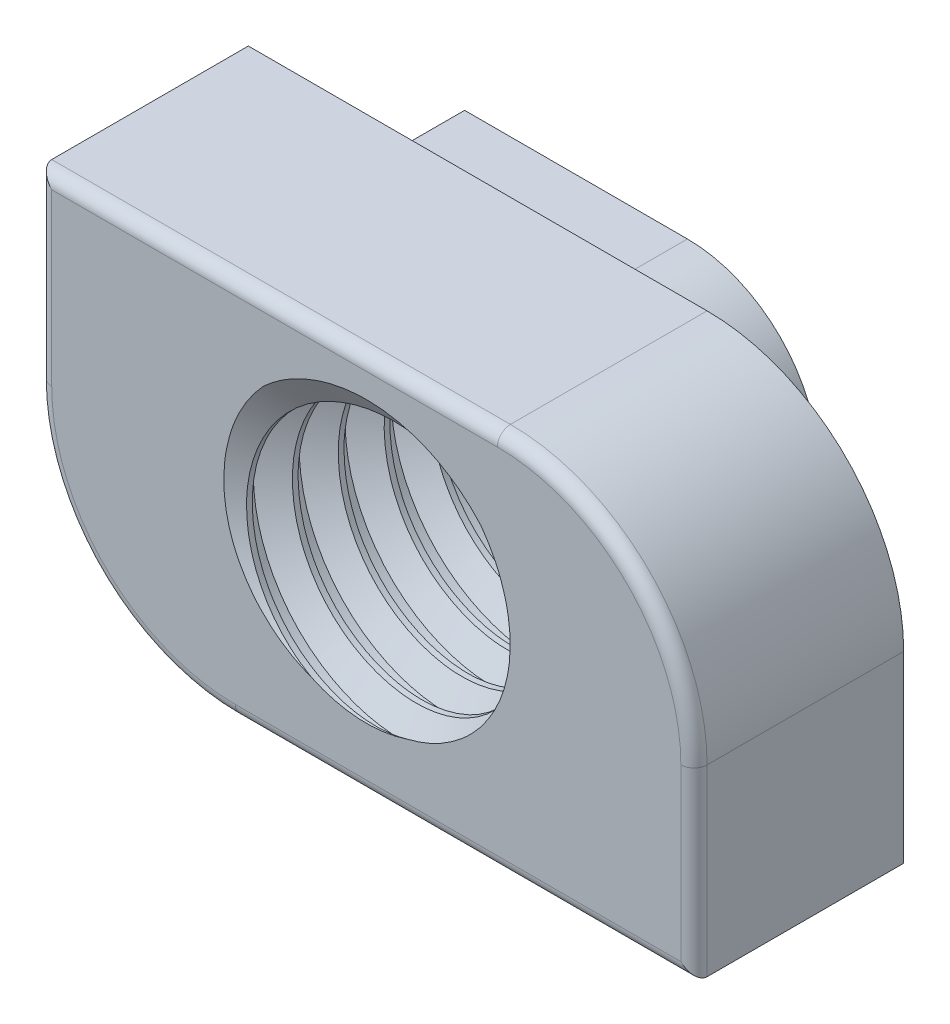
SolidWorks part; units mm, degrees
material "Hierro dúctil (SN)"
ref_plane "Alzado" through (0, 0, 0) normal (0, 0, 1) x (1, 0, 0)
ref_plane "Planta" through (0, 0, 0) normal (0, 1, 0) x (1, 0, 0)
ref_plane "Vista lateral" through (0, 0, 0) normal (1, 0, 0) x (0, 0, -1)
sketch "Croquis1" plane through (0, 0, 0) normal (0, 0, 1) x (1, 0, 0)
  line L0 (0, 0) -> (0, 2.9) construction
  line L1 (-5, 2.9) -> (5, 2.9)
  line L2 (-5, 2.9) -> (-5, -2.9)
  line L3 (-5, -2.9) -> (5, -2.9)
  line L4 (5, 2.9) -> (5, -2.9)
  line L5 (0, 0) -> (5, 0) construction
  dimension "D1" = 5.8
  dimension "D2" = 10
extrude "Saliente-Extruir1" add sketch "Croquis1" along normal blind 3.2 contours L2 L1 L4 L3
sketch "Croquis3" plane through (0, 0, 0) normal (0, 0, -1) x (-1, 0, 0)
  line L0 (0, 2.7) -> (0, 0) construction
  line L1 (0, 0) -> (2.7, 0) construction
  line L2 (-2.7, 2.7) -> (2.7, 2.7)
  line L3 (2.7, 2.7) -> (2.7, -2.7)
  line L4 (2.7, -2.7) -> (-2.7, -2.7)
  line L5 (-2.7, -2.7) -> (-2.7, 2.7)
  point P0 (0, 0)
  dimension "D1" = 5.4
extrude "Saliente-Extruir2" add sketch "Croquis3" along normal blind 1
fillet "Redondeo2" radius 2 2 edges at (-2.7, -2.7, -0.5) (2.7, 2.7, -0.5)
fillet "Redondeo3" radius 3 2 edges at (5, 2.9, 1.6) (-5, -2.9, 1.6)
fillet "Redondeo4" radius 0.2 6 edges at (-1.5, 2.9, 3.2) (1.5, -2.9, 3.2) (4.1213, 2.0213, 3.2) (5, -1.5, 3.2) (-5, 1.5, 3.2) (-4.1213, -2.0213, 3.2)
sketch "Croquis20" plane through (0, 0, -1) normal (0, 0, -1) x (-1, 0, 0)
  point P0 (0, 0)
hole_wizard "Taladro de margen para M3.51" positions "Croquis21" profile "Croquis22" hole size "M3.5" standard "ISO" end condition up to next
sketch "Croquis21" plane through (0, 0, -1) normal (0, 0, -1) x (-1, 0, 0)
  point P0 (0, 0)
sketch "Croquis22" plane through (0, 0, -1) normal (1, 0, 0) x (0, 1, 0)
  line L0 (0, 0) -> (0, 4.2)
  line L1 (0, 4.2) -> (1.95, 4.2)
  line L2 (1.95, 4.2) -> (1.95, 0.025)
  line L3 (1.95, 0.025) -> (1.975, 0)
  line L5 (1.975, 0) -> (0, 0)
  line L6 (-1.95, 0.025) -> (-1.975, 0) construction
  line L11 (0, -6.35) -> (0, 107.95) construction
  dimension "Diámetro de taladro hasta el siguiente" = 3.9
  dimension "Profundidad de taladro hasta el siguiente" = 4.2
  dimension "Diámetro de avellanado cercano" = 3.95
  dimension "Ángulo de avellanado cercano" = 90
thread "Rosca2" pitch 0.7 method cut trim with start face yes trim with end face yes profile "Perfil de rosca4" start angle 0, offset 0.5, length 10, pitch 0.7, diameter 3.9
ref_plane "Plano4" through (1.95, 0, -1.475) normal (0, 1, 0) x (-1, 0, 0)
sketch "Perfil de rosca4" plane through (1.95, 0, -1.475) normal (0, 1, 0) x (-1, 0, 0)
  line L0 (0, 0) -> (0, 0.7) construction
  line L11 (0, 0) -> (0, 0.6125)
  line L12 (0, 0.6125) -> (-0.3789, 0.3937)
  line L13 (-0.3789, 0.3937) -> (-0.3789, 0.2187)
  line L15 (-0.3789, 0.2187) -> (0, 0)
  line L17 (-0.3789, 0.3062) -> (0, 0.3062) construction
  point P2 (0, 0)
  dimension "Pitch" = 0.7
  dimension "Profile_Angle" = 60
  dimension "Profile_Land" = 0.175
  dimension "Profile_Height" = 0.3789
